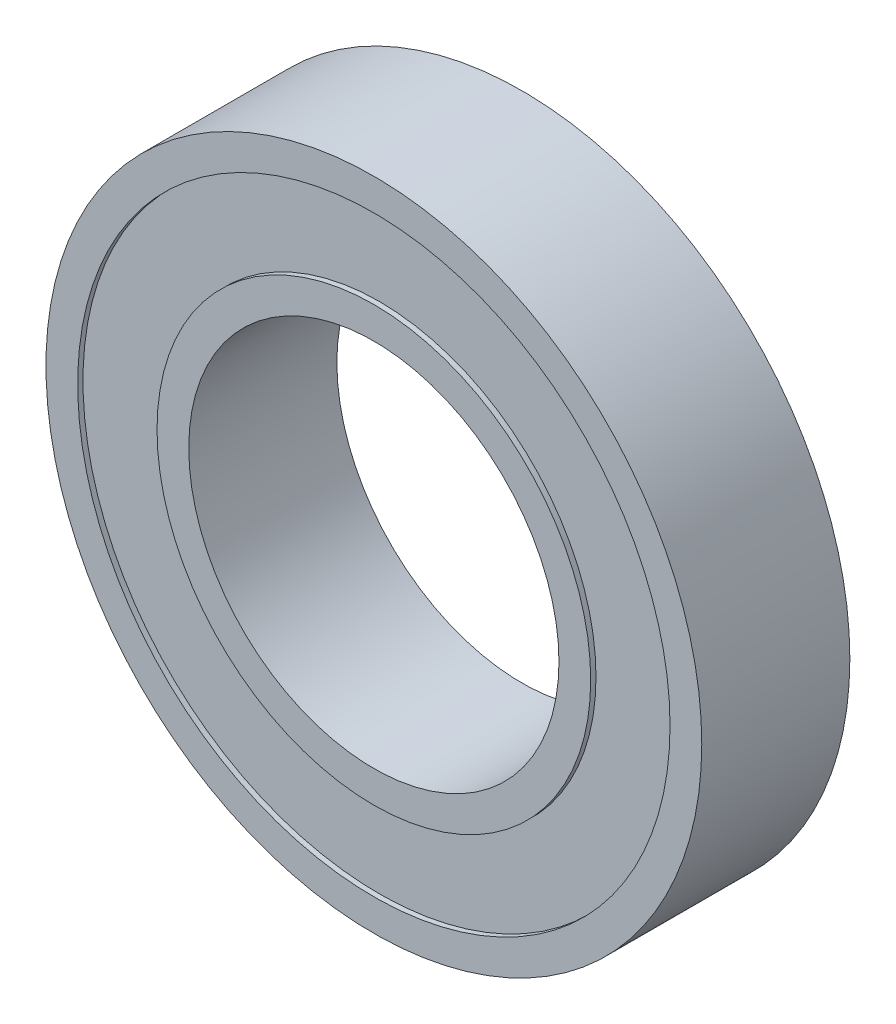
SolidWorks part; units mm, degrees
ref_plane "Front Plane" through (0, 0, 0) normal (1, 0, 0) x (0, 1, 0)
ref_plane "Top Plane" through (0, 0, 0) normal (0, 0, 1) x (0, 1, 0)
ref_plane "Right Plane" through (0, 0, 0) normal (0, 1, 0) x (-1, 0, 0)
sketch "Sketch1" plane through (0, 0, 0) normal (0, 0, 1) x (0, 1, 0)
  circle A0 centre (0, 0) radius 17.5
  circle A1 centre (0, 0) radius 31
  circle A2 centre (0, 0) radius 28
  circle A3 centre (0, 0) radius 20.5
  dimension "D1" = 35
  dimension "D2" = 62
  dimension "D3" = 3
  dimension "D4" = 3
extrude "Boss-Extrude1" add sketch "Sketch1" along normal blind 14 contours A1 A2 | A3 A0 region at (0, -30.1232, 0) region at (0, -19.9202, 0)
extrude "Boss-Extrude2" add sketch "Sketch1<3>" along normal blind 13 from offset 0.5 contours A2 A3 region at (0, -27.208, 0)
sketch "Sketch1<3>" plane through (0, 0, 0) normal (0, 0, 1) x (0, 1, 0) same geometry as "Sketch1"
